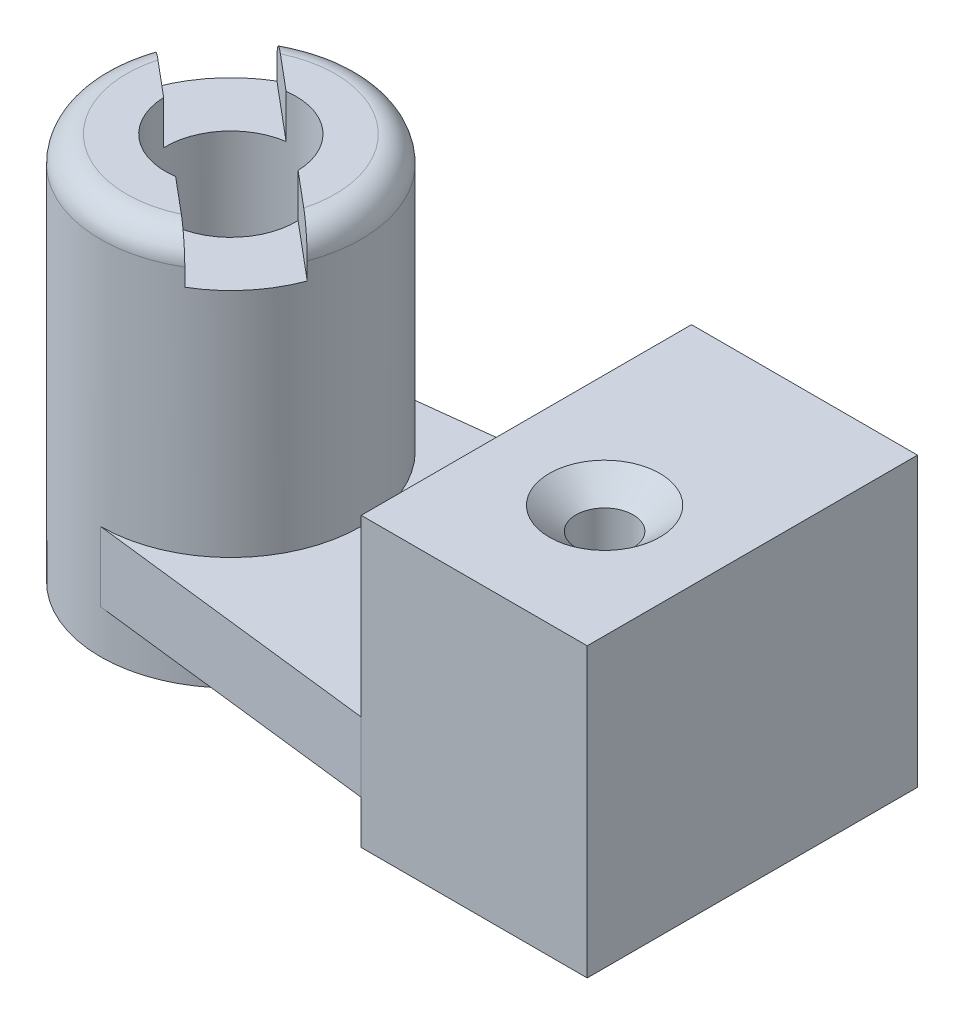
SolidWorks part; units mm, degrees
material "Tungsten"
ref_plane "Front Plane" through (0, 0, 0) normal (0, 0, 1) x (1, 0, 0)
ref_plane "Top Plane" through (0, 0, 0) normal (0, 1, 0) x (1, 0, 0)
ref_plane "Right Plane" through (0, 0, 0) normal (1, 0, 0) x (0, 0, -1)
sketch "Sketch1" plane through (0, 0, 0) normal (0, 1, 0) x (1, 0, 0)
  line L0 (0, 0) -> (-66.04, 0)
  line L1 (-66.04, 0) -> (-66.04, 96.52)
  line L2 (-66.04, 96.52) -> (0, 96.52)
  line L3 (0, 96.52) -> (0, 0)
  line L4 (-66.04, 96.52) -> (-152.4, 86.36)
  line L5 (-66.04, 0) -> (-152.4, 10.16)
  circle A0 centre (-152.4, 48.26) radius 38.1
  circle A1 centre (-152.4, 48.26) radius 19.05
  point P9 (0, 48.26)
  point P11 (-152.4, 86.36)
  dimension "D4" = 76.2
  dimension "D5" = 38.1
  dimension "D1" = 96.52
  dimension "D2" = 66.04
  dimension "D3" = 152.4
extrude "Boss-Extrude1" add sketch "Sketch1" along normal blind 84.074 contours L3 L2 L1 L0 region at (-33.02, 0, -48.26)
extrude "Boss-Extrude2" add sketch "Sketch1<3>" along normal blind 20.32 from offset 12.7 contours A0 L5 L1 L4 region at (-94.8866, 0, -48.26)
sketch "Sketch1<3>" plane through (0, 0, 0) normal (0, 1, 0) x (1, 0, 0) same geometry as "Sketch1"
extrude "Boss-Extrude3" add sketch "Sketch1<4>" along normal blind 113.284 contours A0 A1 region at (-189.4224, 0, -48.26)
sketch "Sketch1<4>" plane through (0, 0, 0) normal (0, 1, 0) x (1, 0, 0) same geometry as "Sketch1"
fillet "Fillet1" radius 7.62 1 edges at (-152.4, 113.284, -10.16)
hole_wizard "CSK for 5/8 Flat Head Machine Screw (100)1" positions "Sketch2" profile "Sketch3" countersink size "5/8" standard "ANSI Inch"
sketch "Sketch2" plane through (0, 84.074, 0) normal (0, 1, 0) x (1, 0, 0)
  line L0 (0, 96.52) -> (0, 0) construction
  line L1 (0, 0) -> (-66.04, 0) construction
  point P0 (-33.02, 38.1)
  point P3 (0, 0)
  dimension "D1" = 33.02
  dimension "D2" = 38.1
sketch "Sketch3" plane through (-33.02, 84.074, -38.1) normal (1, 0, 0) x (0, 0, 1)
  line L0 (0, 0) -> (0, 55.8074)
  line L1 (0, 55.8074) -> (8.3337, 50.8)
  line L2 (8.3337, 50.8) -> (8.3337, 6.5623)
  line L3 (8.3337, 6.5623) -> (16.1544, 0)
  line L5 (16.1544, 0) -> (0, 0)
  line L6 (-8.3337, 6.5623) -> (-16.1544, 0) construction
  line L10 (0, 55.8074) -> (-8.3337, 50.8) construction
  line L11 (0, -6.35) -> (0, 107.95) construction
  dimension "Hole Dia." = 16.6675
  dimension "Hole Depth" = 50.8
  dimension "Near C'Sink Dia." = 32.3088
  dimension "Near C'Sink Angle" = 100
  dimension "Drill Angle" = 118
sketch "Sketch4" plane through (0, 113.284, 0) normal (0, 1, 0) x (1, 0, 0)
  line L0 (-197.9671, 69.9167) -> (-103.3835, -9.4484)
  line L1 (-181.6403, 89.3742) -> (-87.0567, 10.0091)
  line L2 (-66.04, 0) -> (-66.04, 96.52) construction
  line L3 (-103.3835, -9.4484) -> (-87.0567, 10.0091)
  line L4 (-181.6403, 89.3742) -> (-197.9671, 69.9167)
  circle A0 centre (-152.4, 48.26) radius 19.05 construction
  circle A1 centre (-152.4, 48.26) radius 19.05
  circle A2 centre (-152.4, 48.26) radius 12.7
  circle M1 centre (-152.4, 48.26) radius 30.48
  circle M2 centre (-152.4, 48.26) radius 19.05
  dimension "D1" = 25.4
  dimension "D2" = 50
extrude "Cut-Extrude1" cut sketch "Sketch4" against normal blind 12.7 contours L1 L0 M2 M1 | L0 L3 L1 M1 | L1 L0 M1 M2 | L1 L4 L0 M1 region at (-182.4158, 113.284, -73.4462) region at (-170.3979, 113.284, -63.3621) region at (-112.4885, 113.284, -14.7702) region at (-134.4021, 113.284, -33.1579)
equation "\"3.31n\"=0.1"
